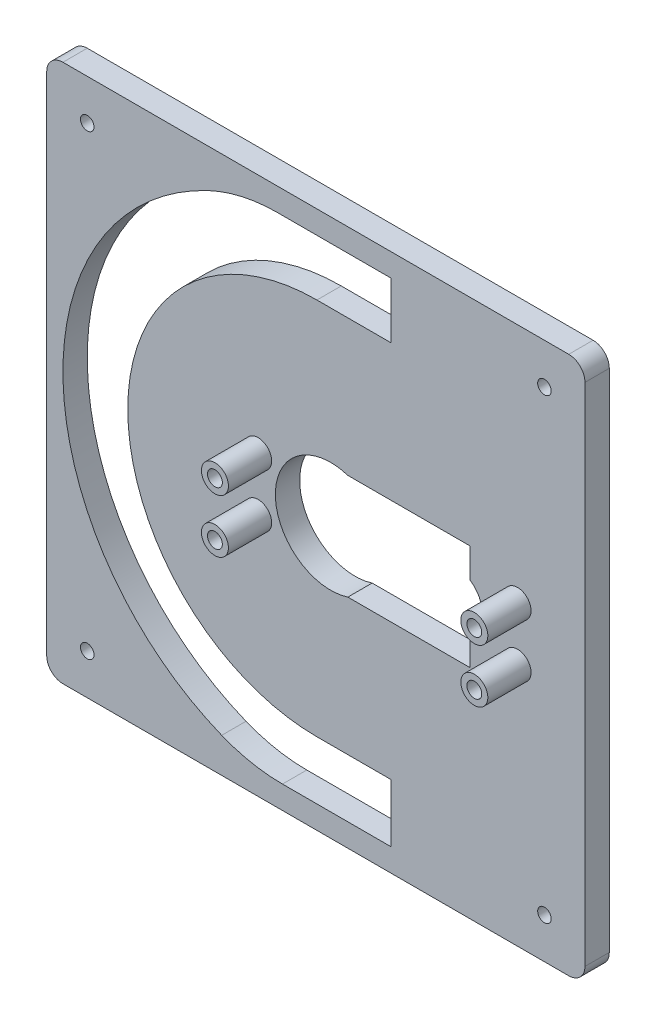
SolidWorks part; units mm, degrees
ref_plane "Front Plane" through (0, 0, 0) normal (0, 0, 1) x (1, 0, 0)
ref_plane "Top Plane" through (0, 0, 0) normal (0, 1, 0) x (1, 0, 0)
ref_plane "Right Plane" through (0, 0, 0) normal (1, 0, 0) x (0, 0, -1)
sketch "Sketch1" plane through (0, 0, 0) normal (0, 0, 1) x (1, 0, 0)
  line L1 (-74.75, 49.6) -> (24.85, 49.6)
  line L2 (-74.75, 49.6) -> (-74.75, -50)
  line L3 (-74.75, -50) -> (24.85, -50)
  line L4 (24.85, 49.6) -> (24.85, -50)
  line L6 (-30.65, 0.0012) -> (-33.35, 0.0012) construction
  line L7 (-15.8956, -0.0011) -> (-5.4456, -0.0011) construction
  circle A0 centre (-22.1047, 0) radius 7.5
  dimension "D3" = 15
  dimension "D8" = 2.7
  dimension "D1" = 99.6
  dimension "D2" = 99.6
  dimension "D5" = 74.75
  dimension "D6" = 50
extrude "Boss-Extrude1" add sketch "Sketch1" along normal blind 3 and the other way blind 1.5
sketch "Sketch20" plane through (0, 0, -1.5) normal (0, 0, -1) x (-1, 0, 0)
  line L0 (-24.85, 49.6) -> (74.75, 49.6) construction
  line L1 (11.0318, 45.36) -> (32.0349, 45.36)
  line L2 (24.75, 35) -> (11.0318, 35)
  line L3 (11.0318, 35) -> (11.0318, 45.36)
  line L4 (11.0318, -45.76) -> (31.1236, -45.76)
  line L5 (24.75, -35) -> (11.0318, -35)
  line L6 (11.0318, -35) -> (11.0318, -45.76)
  line L8 (74.75, -50) -> (-24.85, -50) construction
  arc A0 (42.371, -43.5718) -> (44.8907, 42.4659) centre (24.75, 0) ccw
  arc A1 (24.75, -35) -> (24.75, 35) centre (24.75, 0) ccw
  circle A2 centre (24.75, 0) radius 47 construction
  circle A3 centre (24.75, 0) radius 35 construction
  arc A4 (32.0349, 45.36) -> (44.8907, 42.4659) centre (32.0349, 15.36) cw
  arc A5 (31.1236, -45.76) -> (42.371, -43.5718) centre (31.1236, -15.76) ccw
  dimension "D2" = 24.75
  dimension "D4" = 10.36
  dimension "D6" = 49.6
  dimension "D1" = 35
  dimension "D8" = 30
  dimension "D10" = 30
  dimension "D5" = 10.76
  dimension "D7" = 4.24
  dimension "D9" = 4.24
  dimension "D3" = 12
extrude "Cut-Extrude13" cut sketch "Sketch20" against normal up to surface (4.5 mm away) contours A1 A0 region at (-21.5334, 44.265, -1.5) up to face at (-24.95, -0.2, 3)
sketch "Sketch38" plane through (0, 0, 3) normal (0, 0, 1) x (1, 0, 0)
  line L0 (-22.1047, 0) -> (-36.6047, 0) construction
  circle A0 centre (-35.6241, 5) radius 1.375
  circle A1 centre (-35.6241, -4.9029) radius 1.375
  circle A2 centre (-35.6241, -4.9029) radius 2.5
  circle A3 centre (-35.6241, 5) radius 2.5
  circle A4 centre (12.3759, 5) radius 1.375
  circle A5 centre (12.3759, 5) radius 2.5
  circle A6 centre (12.3759, -4.9029) radius 1.375
  circle A7 centre (12.3759, -4.9029) radius 2.5
  dimension "D1" = 5
  dimension "D3" = 2.75
  dimension "D4" = 2.75
  dimension "D5" = 5
  dimension "D6" = 5
  dimension "D7" = 48
  dimension "D9" = 5
  dimension "D10" = 2.75
  dimension "D11" = 2.75
  dimension "D12" = 5
  dimension "D2" = 5
  dimension "D8" = 48
extrude "Boss-Extrude12" add sketch "Sketch38" along normal blind 8
sketch "Sketch42" plane through (0, 0, -1.5) normal (0, 0, -1) x (-1, 0, 0)
  line L0 (-3.0577, 9.75) -> (19.03, 9.75)
  line L1 (-3.0577, -9.75) -> (19.03, -9.75)
  line L2 (-3.0577, 9.75) -> (-3.0577, 4.2426)
  line L3 (-3.0577, -4.2426) -> (-3.0577, -9.75)
  arc A0 (19.03, -9.75) -> (19.03, 9.75) centre (22.1923, 0) ccw
  arc A1 (-3.0577, 4.2426) -> (-3.0577, -4.2426) centre (0.4423, 0) ccw
  dimension "D2" = 0.4423
  dimension "D3" = 5.5
  dimension "D4" = 9.75
  dimension "D7" = 10.25
  dimension "D1" = 3.0577
  dimension "D5" = 9.75
  dimension "D6" = 19.5
  dimension "D8" = 22.0877
  dimension "D9" = 22.0877
extrude "Cut-Extrude35" cut sketch "Sketch42" against normal blind 10 contours L2 A1 L3 L1 A0 L0 region at (-13.5402, 0, -1.5)
sketch "Sketch43" plane through (0, 0, -1.5) normal (0, 0, -1) x (-1, 0, 0)
  line L0 (-3.0577, -9.75) -> (-3.5577, -9.75)
  line L1 (-3.5577, -9.75) -> (-3.5577, -4.2963)
  line L2 (-3.0577, 9.75) -> (-3.5577, 9.75)
  line L3 (-3.5577, 9.75) -> (-3.5577, 4.2963)
  line L4 (-3.0577, 9.75) -> (-3.0577, 4.5853)
  line L5 (-3.0577, 4.5853) -> (-3.0577, -4.5853)
  line L6 (-3.0577, -4.2426) -> (-3.0577, -9.75) construction
  line L7 (-3.0577, -4.5853) -> (-3.0577, -9.75)
  arc A0 (-3.5577, 4.2963) -> (-3.5577, -4.2963) centre (-0.7407, 0) ccw
  dimension "D1" = 5.1375
  dimension "D2" = 0.7407
  dimension "D5" = 9.75
  dimension "D3" = 0.5
  dimension "D4" = 0.5
  dimension "D6" = 5.1647
  dimension "D7" = 5.1647
extrude "Cut-Extrude36" cut sketch "Sketch43" against normal up to surface (4.5 mm away) up to face at (-6.2069, 0, 3)
sketch "Sketch44" plane through (0, 0, 3) normal (0, 0, 1) x (1, 0, 0)
  circle A0 centre (12.3759, -4.9029) radius 1.5
  circle A1 centre (12.3759, 5) radius 1.5
  circle A2 centre (-35.6241, 5) radius 1.5
  circle A3 centre (-35.6241, -4.9029) radius 1.5
extrude "Cut-Extrude37" cut sketch "Sketch44" against normal blind 2
hole_wizard "M3x0.5 Tapped Hole1" positions "Sketch45" profile "Sketch47" tap size "M3x0.5" standard "ANSI Metric" end condition through all
sketch "Sketch45" plane through (0, 0, -1.5) normal (0, 0, -1) x (-1, 0, 0)
  line L0 (-24.85, -50) -> (-24.85, 49.6) construction
  line L1 (-24.85, 49.6) -> (74.75, 49.6) construction
  line L2 (74.75, 49.6) -> (74.75, -50) construction
  line L3 (74.75, -50) -> (-24.85, -50) construction
  point P0 (-17.35, 42.1)
  point P2 (-17.35, -42.5)
  point P4 (67.25, -42.5)
  point P6 (67.25, 42.1)
  point P15 (-16.4095, 48.6493)
  point P16 (0, 0)
  dimension "D1" = 7.5
  dimension "D2" = 7.5
  dimension "D3" = 7.5
  dimension "D4" = 7.5
  dimension "D5" = 7.5
  dimension "D6" = 7.5
  dimension "D7" = 7.5
  dimension "D8" = 7.5
sketch "Sketch47" plane through (17.35, 42.1, -1.5) normal (1, 0, 0) x (0, 1, 0)
  line L0 (0, 0) -> (0, 12.5)
  line L1 (0, 12.5) -> (1.25, 12.5)
  line L2 (1.25, 12.5) -> (1.25, 0)
  line L5 (1.25, 0) -> (0, 0)
  line L11 (0, -6.35) -> (0, 107.95) construction
  dimension "Thru Tap Drill Dia." = 2.5
  dimension "Thru Tap Drill Depth" = 12.5
cosmetic thread "Hole Thread1" parameters "D2"=3
cosmetic thread "Hole Thread2" parameters "D2"=3
cosmetic thread "Hole Thread3" parameters "D2"=3
cosmetic thread "Hole Thread4" parameters "D2"=3
fillet "Fillet1" radius 3 4 edges at (24.85, 49.6, 0.75) (24.85, -50, 0.75) (-74.75, -50, 0.75) (-74.75, 49.6, 0.75)
